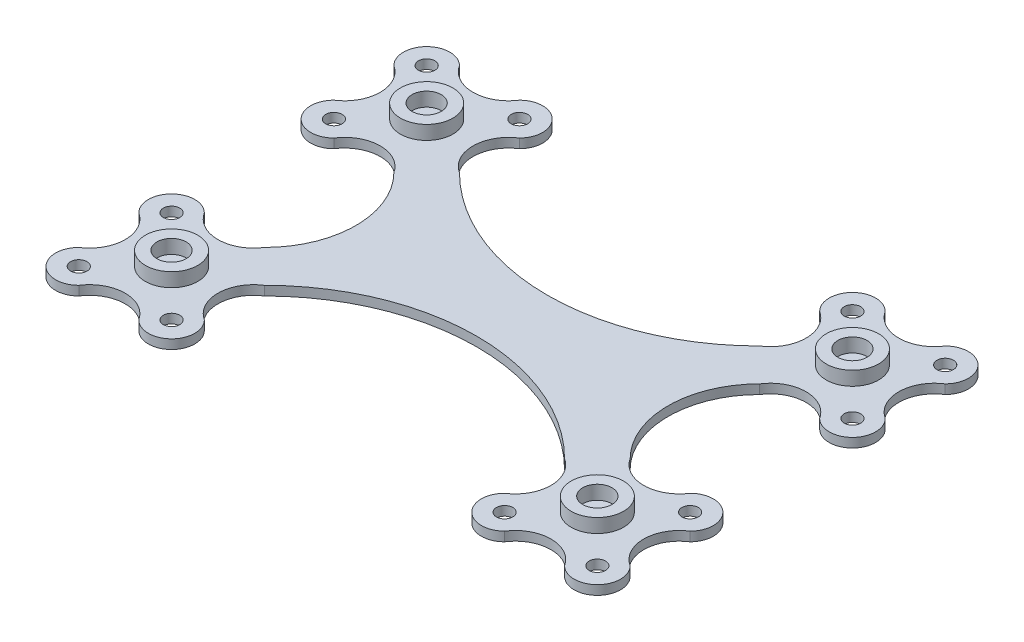
SolidWorks part; units mm, degrees
material "ABS"
ref_plane "Front Plane" through (0, 0, 0) normal (0, 0, 1) x (1, 0, 0)
ref_plane "Top Plane" through (0, 0, 0) normal (0, 1, 0) x (1, 0, 0)
ref_plane "Right Plane" through (0, 0, 0) normal (1, 0, 0) x (0, 0, -1)
sketch "Sketch1" plane through (0, 0, 0) normal (0, 1, 0) x (1, 0, 0)
  line L0 (-17.1901, 8.2099) -> (-8.2099, 17.1901) construction
  line L1 (-12.7, -12.7) -> (12.7, -12.7) construction
  line L2 (-12.7, -12.7) -> (-12.7, 12.7) construction
  line L3 (-12.7, 12.7) -> (12.7, 12.7) construction
  line L4 (12.7, -12.7) -> (12.7, 12.7) construction
  line L5 (-12.7, -12.7) -> (12.7, 12.7) construction
  line L6 (-12.7, 12.7) -> (12.7, -12.7) construction
  line L7 (8.2099, 17.1901) -> (17.1901, 8.2099) construction
  line L8 (-17.1901, -8.2099) -> (-8.2099, -17.1901) construction
  line L9 (8.2099, -17.1901) -> (17.1901, -8.2099) construction
  line L10 (99.3959, 8.2099) -> (108.3761, 17.1901) construction
  line L11 (103.886, -12.7) -> (129.286, -12.7) construction
  line L12 (103.886, -12.7) -> (103.886, 12.7) construction
  line L13 (103.886, 12.7) -> (129.286, 12.7) construction
  line L14 (129.286, -12.7) -> (129.286, 12.7) construction
  line L15 (103.886, -12.7) -> (129.286, 12.7) construction
  line L16 (103.886, 12.7) -> (129.286, -12.7) construction
  line L17 (124.7959, 17.1901) -> (133.7761, 8.2099) construction
  line L18 (99.3959, -8.2099) -> (108.3761, -17.1901) construction
  line L19 (124.7959, -17.1901) -> (133.7761, -8.2099) construction
  line L20 (-17.1901, -61.6401) -> (-8.2099, -52.6599) construction
  line L21 (-12.7, -82.55) -> (12.7, -82.55) construction
  line L22 (-12.7, -82.55) -> (-12.7, -57.15) construction
  line L23 (-12.7, -57.15) -> (12.7, -57.15) construction
  line L24 (12.7, -82.55) -> (12.7, -57.15) construction
  line L25 (-12.7, -82.55) -> (12.7, -57.15) construction
  line L26 (-12.7, -57.15) -> (12.7, -82.55) construction
  line L27 (8.2099, -52.6599) -> (17.1901, -61.6401) construction
  line L28 (-17.1901, -78.0599) -> (-8.2099, -87.0401) construction
  line L29 (8.2099, -87.0401) -> (17.1901, -78.0599) construction
  line L30 (99.3959, -61.6401) -> (108.3761, -52.6599) construction
  line L31 (103.886, -82.55) -> (129.286, -82.55) construction
  line L32 (103.886, -82.55) -> (103.886, -57.15) construction
  line L33 (103.886, -57.15) -> (129.286, -57.15) construction
  line L34 (129.286, -82.55) -> (129.286, -57.15) construction
  line L35 (103.886, -82.55) -> (129.286, -57.15) construction
  line L36 (103.886, -57.15) -> (129.286, -82.55) construction
  line L37 (124.7959, -52.6599) -> (133.7761, -61.6401) construction
  line L38 (99.3959, -78.0599) -> (108.3761, -87.0401) construction
  line L39 (124.7959, -87.0401) -> (133.7761, -78.0599) construction
  line L40 (12.7, -12.7) -> (103.886, -57.15) construction
  line L41 (12.7, -57.15) -> (103.886, -12.7) construction
  circle A0 centre (-12.7, 12.7) radius 6.35
  circle A1 centre (12.7, 12.7) radius 6.35
  circle A2 centre (12.7, -12.7) radius 6.35
  circle A3 centre (-12.7, -12.7) radius 6.35
  circle A4 centre (0, 0) radius 7.175
  circle A5 centre (0, 0) radius 4
  arc A6 (-8.2099, 17.1901) -> (8.2099, 17.1901) centre (0, 22.4506) ccw
  arc A7 (-17.1901, 8.2099) -> (-17.1901, -8.2099) centre (-22.4506, 0) cw
  arc A8 (-8.2099, -17.1901) -> (8.2099, -17.1901) centre (0, -22.4506) cw
  arc A9 (17.1901, -8.2099) -> (17.1901, 8.2099) centre (22.4506, 0) cw
  circle A10 centre (103.886, 12.7) radius 6.35
  circle A11 centre (129.286, 12.7) radius 6.35
  circle A12 centre (129.286, -12.7) radius 6.35
  circle A13 centre (103.886, -12.7) radius 6.35
  circle A14 centre (116.586, 0) radius 7.175
  circle A15 centre (116.586, 0) radius 4
  arc A16 (108.3761, 17.1901) -> (124.7959, 17.1901) centre (116.586, 22.4506) ccw
  arc A17 (99.3959, 8.2099) -> (99.3959, -8.2099) centre (94.1354, 0) cw
  arc A18 (108.3761, -17.1901) -> (124.7959, -17.1901) centre (116.586, -22.4506) cw
  arc A19 (133.7761, -8.2099) -> (133.7761, 8.2099) centre (139.0366, 0) cw
  circle A20 centre (-12.7, -57.15) radius 6.35
  circle A21 centre (12.7, -57.15) radius 6.35
  circle A22 centre (12.7, -82.55) radius 6.35
  circle A23 centre (-12.7, -82.55) radius 6.35
  circle A24 centre (0, -69.85) radius 7.175
  circle A25 centre (0, -69.85) radius 4
  arc A26 (-8.2099, -52.6599) -> (8.2099, -52.6599) centre (0, -47.3994) ccw
  arc A27 (-17.1901, -61.6401) -> (-17.1901, -78.0599) centre (-22.4506, -69.85) cw
  arc A28 (-8.2099, -87.0401) -> (8.2099, -87.0401) centre (0, -92.3006) cw
  arc A29 (17.1901, -78.0599) -> (17.1901, -61.6401) centre (22.4506, -69.85) cw
  circle A30 centre (103.886, -57.15) radius 6.35
  circle A31 centre (129.286, -57.15) radius 6.35
  circle A32 centre (129.286, -82.55) radius 6.35
  circle A33 centre (103.886, -82.55) radius 6.35
  circle A34 centre (116.586, -69.85) radius 7.175
  circle A35 centre (116.586, -69.85) radius 4
  arc A36 (108.3761, -52.6599) -> (124.7959, -52.6599) centre (116.586, -47.3994) ccw
  arc A37 (99.3959, -61.6401) -> (99.3959, -78.0599) centre (94.1354, -69.85) cw
  arc A38 (108.3761, -87.0401) -> (124.7959, -87.0401) centre (116.586, -92.3006) cw
  arc A39 (133.7761, -78.0599) -> (133.7761, -61.6401) centre (139.0366, -69.85) cw
  arc A40 (8.2099, -17.1901) -> (8.2099, -52.6599) centre (-9.525, -34.925) cw
  arc A41 (17.1901, -8.2099) -> (99.3959, -8.2099) centre (58.293, 32.893) ccw
  arc A42 (108.3761, -17.1901) -> (108.3761, -52.6599) centre (126.111, -34.925) ccw
  arc A43 (99.3959, -61.6401) -> (17.1901, -61.6401) centre (58.293, -102.743) ccw
  point P0 (0, 0)
  point P16 (-12.7, 12.7)
  point P19 (12.7, 12.7)
  point P22 (-12.7, -12.7)
  point P25 (12.7, -12.7)
  point P29 (116.586, 0)
  point P44 (103.886, 12.7)
  point P47 (129.286, 12.7)
  point P50 (103.886, -12.7)
  point P53 (129.286, -12.7)
  point P57 (0, -69.85)
  point P72 (-12.7, -57.15)
  point P75 (12.7, -57.15)
  point P78 (-12.7, -82.55)
  point P81 (12.7, -82.55)
  point P85 (116.586, -69.85)
  point P100 (103.886, -57.15)
  point P103 (129.286, -57.15)
  point P106 (103.886, -82.55)
  point P109 (129.286, -82.55)
  dimension "D1" = 8
  dimension "D2" = 12.7
  dimension "D3" = 3.175
  dimension "D5" = 8
  dimension "D6" = 12.7
  dimension "D9" = 8
  dimension "D10" = 12.7
  dimension "D13" = 8
  dimension "D14" = 12.7
  dimension "D15" = 14.35
  dimension "D17" = 14.35
  dimension "D18" = 14.35
  dimension "D19" = 25.0809
  dimension "D20" = 25.0809
  dimension "D21" = 58.1282
  dimension "D22" = 58.1282
  dimension "D4" = 25.4
  dimension "D7" = 69.85
  dimension "D8" = 25.4
  dimension "D11" = 116.586
  dimension "D12" = 25.4
  dimension "D16" = 25.4
extrude "Boss-Extrude1" add sketch "Sketch1" along normal blind 2.54 contours A3 A8 A7 | A2 A9 A1 A6 A0 A7 A3 A8 A4 | A2 A9 A8 | A1 A9 A6 | A4 A5 | A5 | A0 A7 A6 | A43 A30 A42 A13 A41 A2 A40 A21 | A20 A27 A26 | A22 A29 A21 A26 A20 A27 A23 A28 A24 | A23 A28 A27 | A24 A25 | A22 A29 A28 | A21 A29 A26 | A33 A38 A37 | A30 A37 A36 | A32 A39 A31 A36 A30 A37 A33 A38 A34 | A31 A39 A36 | A32 A39 A38 | A13 A18 A17 | A12 A19 A11 A16 A10 A17 A13 A18 A14 | A34 A35 | A25 | A35 | A10 A17 A16 | A14 A15 | A15 | A11 A19 A16 | A12 A19 A18 region at (-12.7009, 0, -12.7009) region at (0, 0, -12.2509) region at (12.7009, 0, -12.7009) region at (-12.7009, 0, 12.7009) region at (12.7009, 0, 12.7009) region at (58.293, 0, 34.925) region at (103.8851, 0, 12.7009) region at (104.3351, 0, 0) region at (12.7009, 0, 57.1491) region at (103.8851, 0, 57.1491) region at (103.8851, 0, -12.7009) region at (7.8923, 0, 61.9577) region at (129.2869, 0, 12.7009) region at (116.586, 0, 57.5991) region at (-12.7009, 0, 57.1491) region at (129.2869, 0, 57.1491) region at (12.7009, 0, 82.5509) region at (129.2869, 0, -12.7009) region at (103.8851, 0, 82.5509) region at (129.2869, 0, 82.5509) region at (-12.7009, 0, 82.5509) region at (-6.9721, 0, 0) region at (0, 0, 0) region at (109.6139, 0, 0) region at (116.586, 0, 0) region at (-6.9721, 0, 69.85) region at (0, 0, 69.85) region at (109.6139, 0, 69.85) region at (116.586, 0, 69.85)
extrude "Boss-Extrude2" add sketch "Sketch1<4>" along normal blind 6.35 contours A4 A5 | A14 A15 | A24 A25 | A34 A35 region at (-6.9721, 0, 0) region at (109.6139, 0, 0) region at (-6.9721, 0, 69.85) region at (109.6139, 0, 69.85)
sketch "Sketch1<4>" plane through (0, 0, 0) normal (0, 1, 0) x (1, 0, 0) same geometry as "Sketch1"
hole_wizard "#8 Clearance Hole2" positions "Sketch6" profile "Sketch7" hole size "#8" standard "ANSI Inch" end condition through all
sketch "Sketch6" plane through (0, 2.54, 0) normal (0, 1, 0) x (1, 0, 0)
  point P0 (103.886, 12.7)
  point P3 (129.286, 12.7)
  point P6 (129.286, -12.7)
  point P9 (129.286, -57.15)
  point P12 (129.286, -82.55)
  point P15 (103.886, -82.55)
  point P18 (12.7, -82.55)
  point P21 (-12.7, -82.55)
  point P24 (-12.7, -57.15)
  point P28 (-12.7, -12.7)
  point P31 (-12.7, 12.7)
  point P34 (12.7, 12.7)
sketch "Sketch7" plane through (103.886, 2.54, -12.7) normal (1, 0, 0) x (0, 0, 1)
  line L0 (0, 0) -> (0, 2.54)
  line L1 (0, 2.54) -> (2.2479, 2.54)
  line L2 (2.2479, 2.54) -> (2.2479, 0)
  line L5 (2.2479, 0) -> (0, 0)
  line L11 (0, -6.35) -> (0, 107.95) construction
  dimension "Thru Hole Dia." = 4.4958
  dimension "Thru Hole Depth" = 2.54
